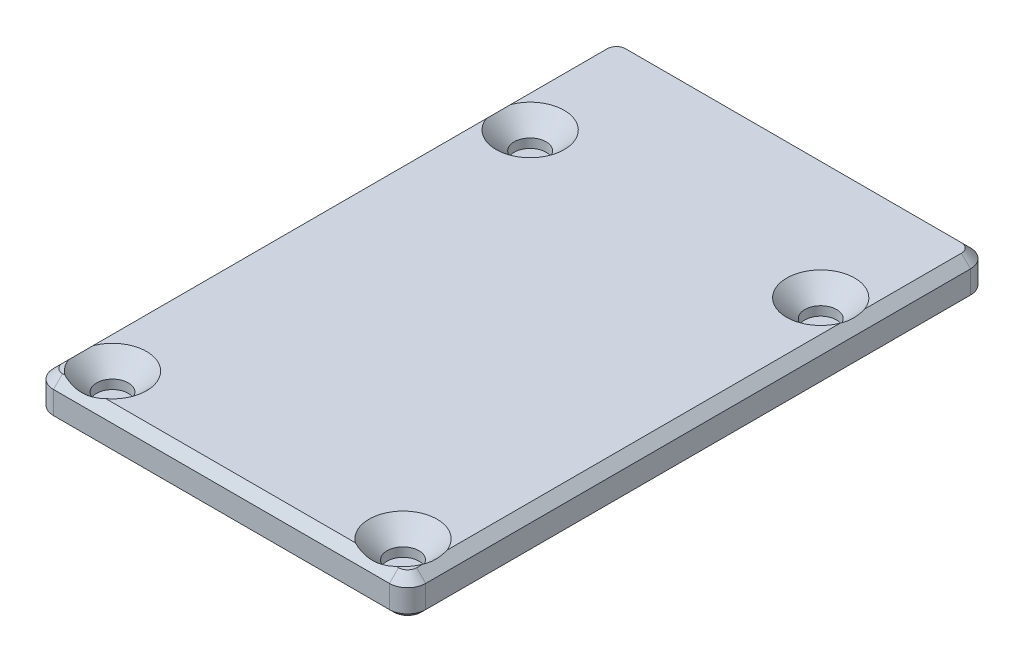
SolidWorks part; units mm, degrees
ref_plane "Спереди" through (0, 0, 0) normal (0, 0, 1) x (1, 0, 0)
ref_plane "Сверху" through (0, 0, 0) normal (0, 1, 0) x (1, 0, 0)
ref_plane "Справа" through (0, 0, 0) normal (1, 0, 0) x (0, 0, -1)
sketch "Эскиз1" plane through (0, 0, 0) normal (0, 1, 0) x (1, 0, 0)
  line L1 (-20.5, -32) -> (20.5, -32)
  line L2 (-20.5, -32) -> (-20.5, 32)
  line L3 (-20.5, 32) -> (20.5, 32)
  line L4 (20.5, -32) -> (20.5, 32)
  line L5 (0, 32) -> (0, -32) construction
  line L6 (-20.5, 0) -> (20.5, 0) construction
  point P0 (0, 0)
  dimension "D1" = 64
  dimension "D2" = 41
extrude "Бобышка-Вытянуть1" add sketch "Эскиз1" along normal blind 4
sketch "Эскиз2" plane through (0, 4, 0) normal (0, 1, 0) x (1, 0, 0)
  line L0 (0, 32.2776) -> (0, 0) construction
  line L1 (0, 0) -> (26.8846, 0) construction
  line L2 (20.5, -32) -> (20.5, 32) construction
  circle A0 centre (16, 18) radius 1.75
  circle A1 centre (16, -28) radius 1.75
  circle A3 centre (-16, 18) radius 1.75
  circle A4 centre (-16, -28) radius 1.75
  dimension "D1" = 18
  dimension "D2" = 4.5
  dimension "D3" = 3.5
  dimension "D4" = 46
  dimension "D5" = 32
extrude "Вырез-Вытянуть1" cut sketch "Эскиз2" against normal blind 3
fillet "Скругление1" radius 2 4 edges at (20.5, 2, -32) (-20.5, 2, -32) (-20.5, 2, 32) (20.5, 2, 32)
sketch "Эскиз3" plane through (0, 0, 0) normal (0, -1, 0) x (1, 0, 0)
  line L0 (0, 32.2375) -> (0, 0) construction
  line L1 (0, 0) -> (33.8614, 0) construction
  line L2 (-18.5, 32) -> (18.5, 32) construction
  line L3 (-12.5, 24) -> (12.5, 24)
  line L4 (-12.5, 24) -> (-12.5, 32)
  line L5 (-12.5, 32) -> (12.5, 32)
  line L6 (12.5, 24) -> (12.5, 32)
  line L7 (0, 32) -> (0, 24) construction
  line L8 (-12.5, 28) -> (12.5, 28) construction
  point P3 (0, 28)
  dimension "D1" = 25
  dimension "D2" = 8
extrude "Бобышка-Вытянуть2" [suppressed] add sketch "Эскиз3" along normal blind 5
fillet "Скругление2" [suppressed] radius 1
chamfer "Фаска2" distance 1 angle 45 8 edges at (-20.5, 4, 0) (19.9142, 4, -31.4142) (-19.9142, 4, -31.4142) (0, 4, -32) (-19.9142, 4, 31.4142) (0, 4, 32) (19.9142, 4, 31.4142) (20.5, 4, 0)
chamfer "Фаска1" distance 2 angle 45 4 edges at (16, 4, 26.25) (-16, 4, -19.75) (16, 4, -16.25) (-16, 4, 29.75)
sketch "Эскиз4" plane through (0, 4, 0) normal (0, 1, 0) x (1, 0, 0)
  line L0 (23.4186, 22.1575) -> (1.1874, 22.1575)
  line L1 (23.4186, 10.6017) -> (2.0235, 10.6017)
  line L2 (23.4186, 28.2171) -> (23.4186, 3.4703) construction
  line L3 (23.4186, 22.1575) -> (23.4186, 10.6017)
  arc A0 (1.1874, 22.1575) -> (2.0235, 10.6017) centre (-0.0813, 16.2575) ccw
extrude "Вырез-Вытянуть3" [suppressed] cut sketch "Эскиз4" against normal blind 10
chamfer "Фаска3" distance 0.5 angle 45 8 edges at (-19.9142, 0, -31.4142) (-20.5, 0, 0) (-19.9142, 0, 31.4142) (0, 0, 32) (19.9142, 0, 31.4142) (20.5, 0, 0) (19.9142, 0, -31.4142) (0, 0, -32)
